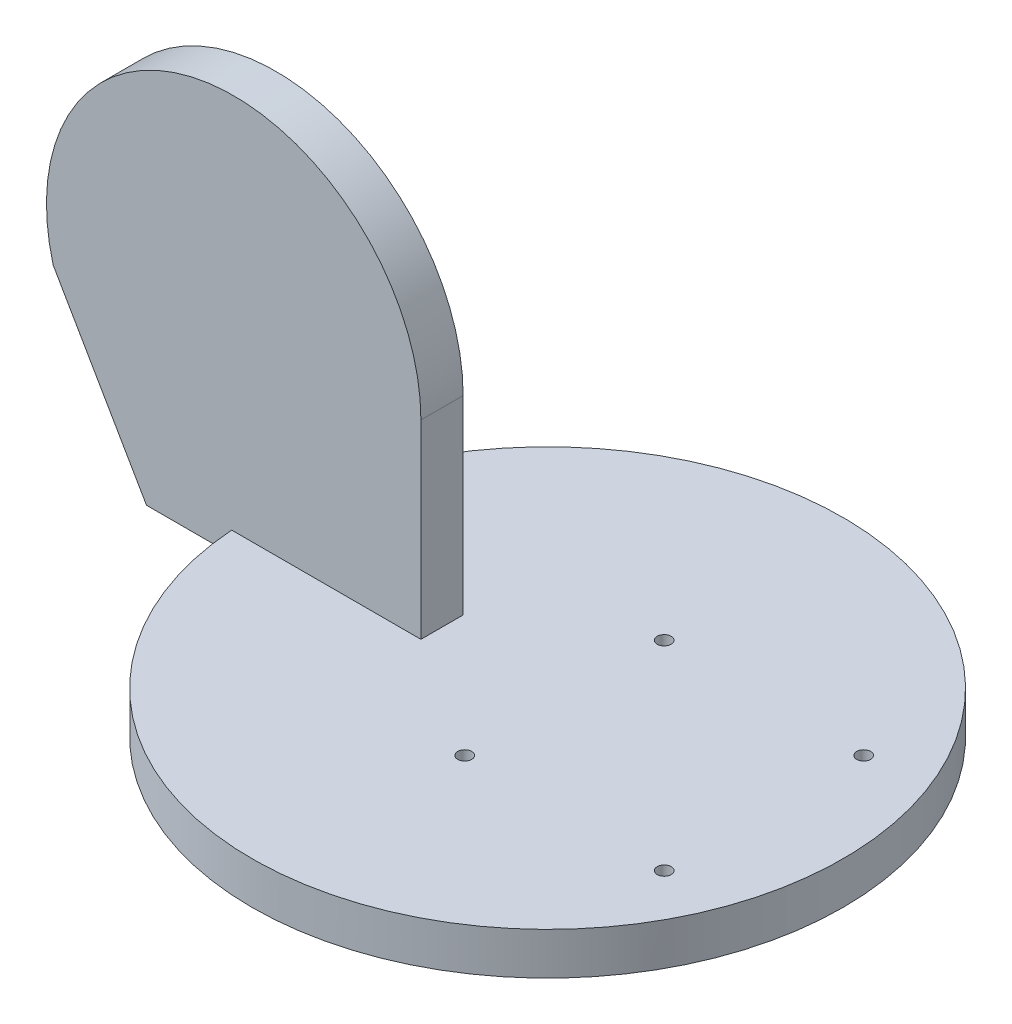
SolidWorks part; units mm, degrees
ref_plane "Front Plane" through (0, 0, 0) normal (0, 0, 1) x (1, 0, 0)
ref_plane "Top Plane" through (0, 0, 0) normal (0, 1, 0) x (1, 0, 0)
ref_plane "Right Plane" through (0, 0, 0) normal (1, 0, 0) x (0, 0, -1)
sketch "Sketch1" plane through (0, 0, 0) normal (0, 1, 0) x (1, 0, 0)
  circle A0 centre (0, 0) radius 70
  dimension "D1" = 140
extrude "Boss-Extrude1" add sketch "Sketch1" along normal blind 10
sketch "Sketch2" plane through (0, 0, 0) normal (0, -1, 0) x (1, 0, 0)
  circle A2 centre (0, 0) radius 65
  circle A3 centre (0, 0) radius 65
  dimension "D1" = 5
extrude "Boss-Extrude2" add sketch "Sketch2" along normal blind 3
sketch "Sketch3" plane through (0, 0, 0) normal (0, 0, 1) x (1, 0, 0)
  line L3 (-25, 55) -> (-25, 5)
  line L4 (-25, 5) -> (-90, 5)
  line L5 (-90, 5) -> (-112.0943, 43.2048)
  arc A2 (-112.0943, 43.2048) -> (-25, 55) centre (-69.3458, 55) cw
  point P5 (0, 0)
  point P6 (0, 0)
  point P7 (-82.6042, 16.8564)
  point P8 (0, 0)
  point P9 (0, 0)
  point P10 (-53.1999, 6.6194)
  point P11 (-25, 10.1043)
  point P13 (-77.3768, 25.351)
  point P14 (-75.1987, 6.6194)
  point P15 (-93.7125, 32.3209)
  point P16 (0, 0)
  point P17 (0, 0)
  point P18 (-82.9091, 4.7985)
  point P19 (0, 0)
  point P20 (0, 0)
  dimension "D1" = 25
  dimension "D3" = 65
  dimension "D2" = 5
  dimension "D4" = 50
extrude "Boss-Extrude3" add sketch "Sketch3" along normal mid plane 10
hole_wizard "M4x0.7 Tapped Hole1" positions "Sketch4" profile "Sketch5" tap size "M4x0.7" standard "ANSI Metric"
sketch "Sketch4" plane through (0, 10, 0) normal (0, 1, 0) x (1, 0, 0)
  point P0 (4, 23.622)
  point P2 (51.244, 23.622)
  point P4 (51.244, -23.622)
  point P6 (4, -23.622)
  point P9 (0, 0)
  point P10 (0, 0)
  point P11 (0, 0)
  point P12 (0, 0)
  point P18 (73.345, -16.0634)
  dimension "D1" = 47.244
  dimension "D2" = 47.244
  dimension "D3" = 4
  dimension "D4" = 23.622
sketch "Sketch5" plane through (4, 10, -23.622) normal (1, 0, 0) x (0, 0, 1)
  line L0 (0, 0) -> (0, 11.0914)
  line L1 (0, 11.0914) -> (1.65, 10.1)
  line L2 (1.65, 10.1) -> (1.65, 0)
  line L5 (1.65, 0) -> (0, 0)
  line L10 (0, 11.0914) -> (-1.65, 10.1) construction
  line L11 (0, -6.35) -> (0, 107.95) construction
  dimension "Tap Drill Dia." = 3.3
  dimension "Tap Drill Depth" = 10.1
  dimension "Drill Angle" = 118
cosmetic thread "Hole Thread1" parameters "D1"=8, "D2"=4
cosmetic thread "Hole Thread2" parameters "D1"=8, "D2"=4
cosmetic thread "Hole Thread3" parameters "D1"=8, "D2"=4
cosmetic thread "Hole Thread4" parameters "D1"=8, "D2"=4
